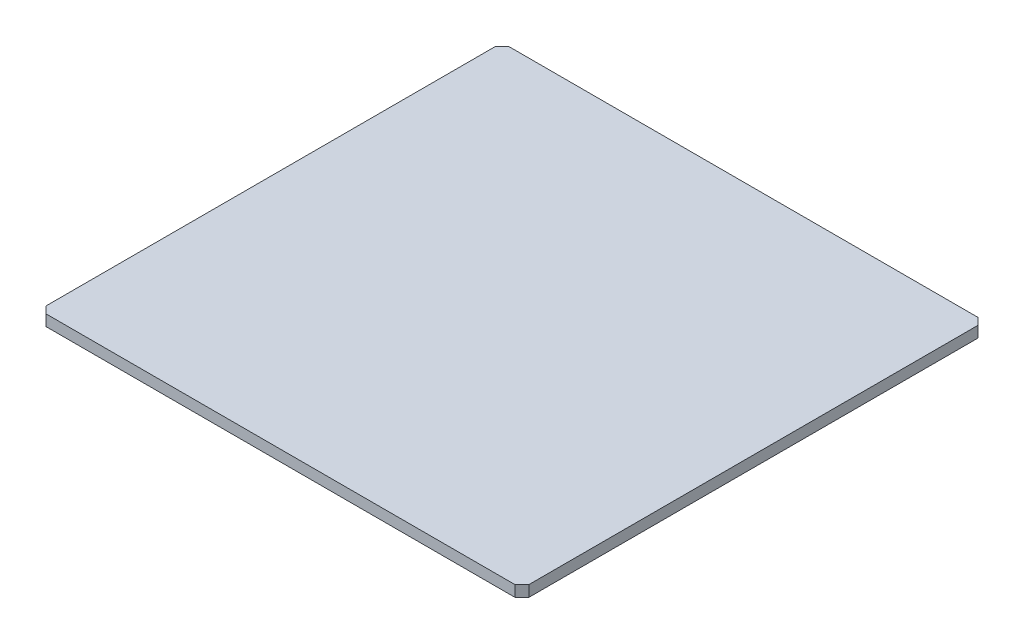
SolidWorks part; units mm, degrees
ref_plane "Front Plane" through (0, 0, 0) normal (0, 0, 1) x (1, 0, 0)
ref_plane "Top Plane" through (0, 0, 0) normal (0, 1, 0) x (1, 0, 0)
ref_plane "Right Plane" through (0, 0, 0) normal (1, 0, 0) x (0, 0, -1)
sketch "Sketch1" plane through (0, 0, 0) normal (0, 1, 0) x (1, 0, 0)
  line L0 (0.15, 94.1858) -> (1.5642, 95.6)
  line L1 (0.15, 0) -> (99.85, 0) construction
  line L2 (0.15, 0) -> (0.15, 95.6) construction
  line L3 (0.15, 95.6) -> (99.85, 95.6) construction
  line L4 (99.85, 0) -> (99.85, 95.6) construction
  line L5 (1.5642, 95.6) -> (98.4358, 95.6)
  line L6 (98.4358, 95.6) -> (99.85, 94.1858)
  line L7 (99.85, 94.1858) -> (99.85, 1.4142)
  line L8 (99.85, 1.4142) -> (98.4358, 0)
  line L9 (98.4358, 0) -> (1.5642, 0)
  line L10 (1.5642, 0) -> (0.15, 1.4142)
  line L11 (0.15, 1.4142) -> (0.15, 94.1858)
extrude "Boss-Extrude1" add sketch "Sketch1" along normal blind 2.286
ref_plane "center-of-slot" through (0, 1.143, 0) normal (0, 1, 0) x (1, 0, 0)
